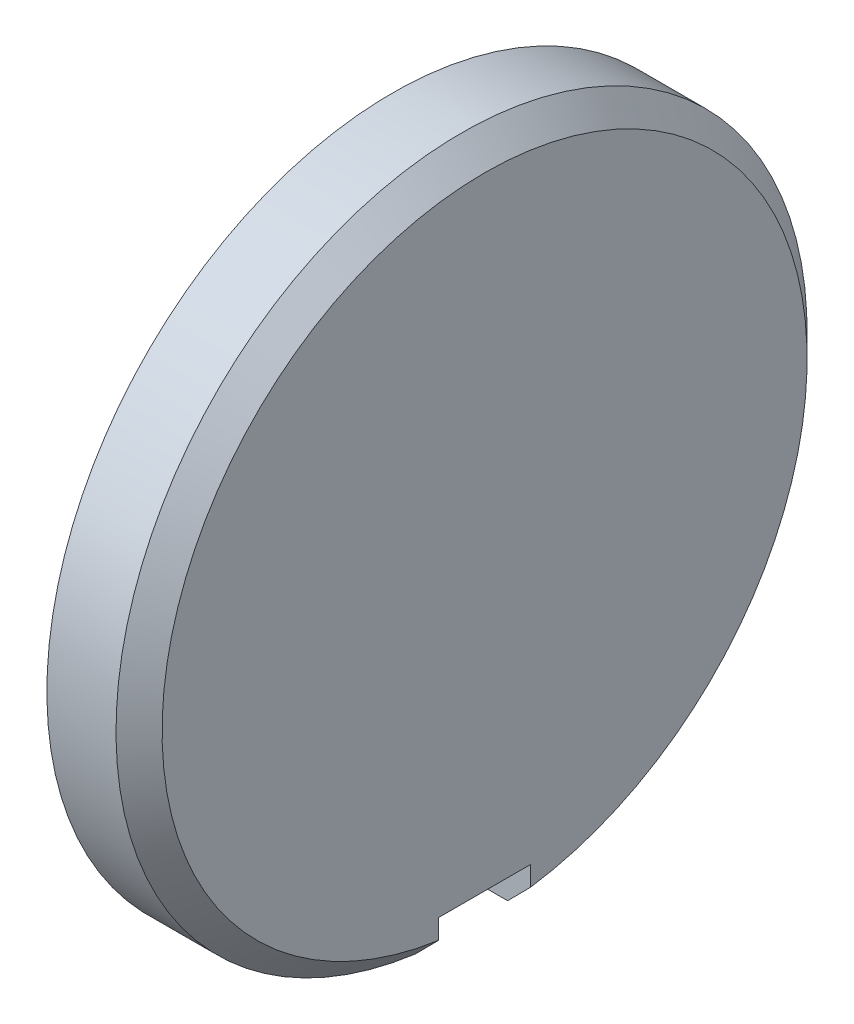
SolidWorks part; units mm, degrees
ref_plane "Front Plane" through (0, 0, 0) normal (0, 0, 1) x (1, 0, 0)
ref_plane "Top Plane" through (0, 0, 0) normal (0, 1, 0) x (1, 0, 0)
ref_plane "Right Plane" through (0, 0, 0) normal (1, 0, 0) x (0, 0, -1)
ref_plane "Plane1" through (0, 0, 66) normal (0, 0, 1) x (1, 0, 0)
sketch "Sketch1" plane through (0, 0, 66) normal (0, 0, 1) x (1, 0, 0)
  line L0 (69, -20) -> (81.8, -20) construction
  line L1 (74, -17.7) -> (75.2, -17.7)
  line L2 (75.2, -17.7) -> (75.2, -20)
  line L3 (75.2, -20) -> (76.8, -20)
  line L4 (76.8, -20) -> (76.8, -14.4)
  line L5 (76.8, -14.4) -> (76.4, -14)
  line L6 (76.4, -14) -> (75.2, -14)
  line L7 (75.2, -14) -> (75.2, -17)
  line L8 (75.2, -17) -> (74, -17)
  line L9 (74, -17) -> (74, -17.7)
revolve "Revolve1" add sketch "Sketch1" angle 360 about L0
sketch "Sketch2" plane through (0, 0, 0) normal (0, 0, 1) x (1, 0, 0)
  line L1 (73.9, -20.4) -> (75.18, -20.4)
  line L2 (73.9, -20.4) -> (73.9, -19.6)
  line L3 (73.9, -19.6) -> (75.18, -19.6)
  line L4 (75.18, -20.4) -> (75.18, -19.6)
extrude "Boss-Extrude1" add sketch "Sketch2" along normal blind 6.4 from offset 62.8 separate body
combine bodies "Combine1" operation type subtract main body 101 bodies to subtract 102
sketch "Sketch3" plane through (0, 0, 0) normal (0, 0, 1) x (1, 0, 0)
  line L1 (73.9, -23.2) -> (75.18, -23.2)
  line L2 (73.9, -23.2) -> (73.9, -16.8)
  line L3 (73.9, -16.8) -> (75.18, -16.8)
  line L4 (75.18, -23.2) -> (75.18, -16.8)
extrude "Boss-Extrude2" add sketch "Sketch3" along normal blind 0.8 from offset 65.6 separate body
combine bodies "Combine2" operation type subtract main body 103 bodies to subtract 104
sketch "Sketch4" plane through (0, 0, 0) normal (0, 0, 1) x (1, 0, 0)
  line L1 (75.1, -26.1) -> (76.9, -26.1)
  line L2 (75.1, -26.1) -> (75.1, -25.2)
  line L3 (75.1, -25.2) -> (76.9, -25.2)
  line L4 (76.9, -26.1) -> (76.9, -25.2)
extrude "Boss-Extrude3" add sketch "Sketch4" along normal blind 1.6 from offset 65.2 separate body
combine bodies "Combine3" operation type subtract main body 105 bodies to subtract 106
